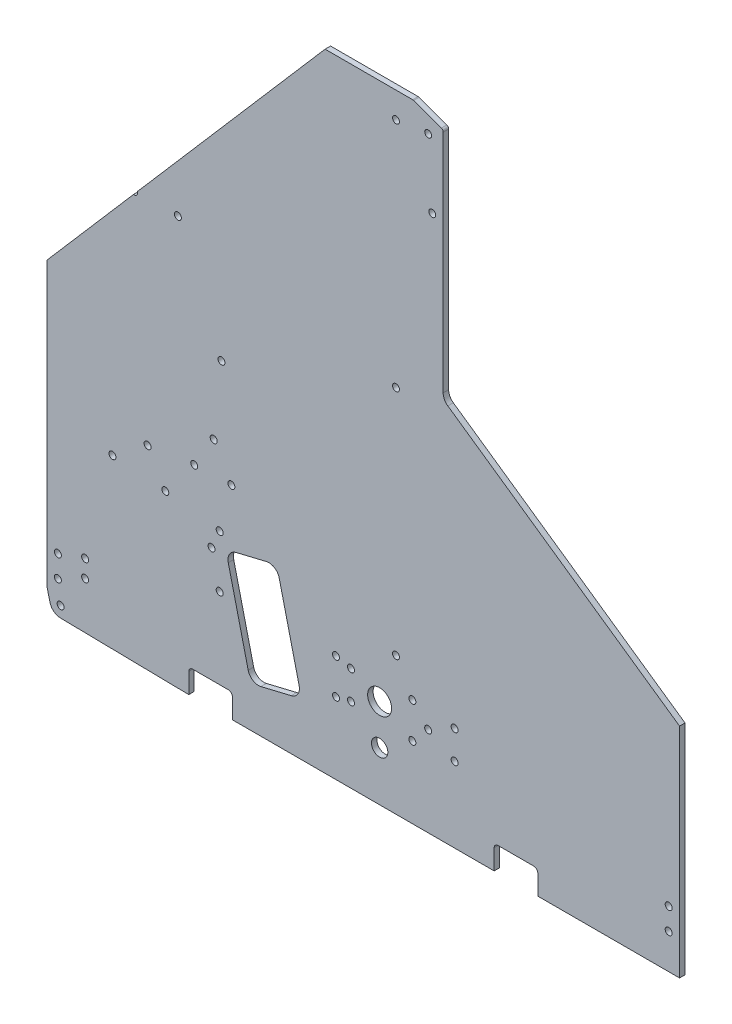
SolidWorks part; units mm, degrees
ref_plane "Front Plane" through (0, 0, 0) normal (0, 0, 1) x (1, 0, 0)
ref_plane "Top Plane" through (0, 0, 0) normal (0, 1, 0) x (1, 0, 0)
ref_plane "Right Plane" through (0, 0, 0) normal (1, 0, 0) x (0, 0, -1)
sketch "Sketch1" plane through (0, 0, 0) normal (0, 0, 1) x (1, 0, 0)
  line L0 (82.55, -20.32) -> (82.55, -6.35)
  line L2 (0, 0) -> (0, 157.48)
  line L4 (368.3, -20.32) -> (368.3, 106.68)
  line L5 (82.55, -6.35) -> (107.95, -6.35)
  line L6 (107.95, -6.35) -> (107.95, -20.32)
  line L7 (107.95, -20.32) -> (260.35, -20.32)
  line L8 (260.35, -20.32) -> (260.35, -6.35)
  line L9 (260.35, -6.35) -> (285.75, -6.35)
  line L10 (285.75, -6.35) -> (285.75, -20.32)
  line L11 (285.75, -20.32) -> (368.3, -20.32)
  line L12 (361.95, 12.7) -> (368.3, 12.7) construction
  line L13 (0, 0) -> (6.35, 0) construction
  line L14 (0.1896, -7.8901) -> (1.7771, -14.2401)
  line L15 (7.8295, -19.0491) -> (82.55, -20.32)
  line L16 (0, 0) -> (0, -6.35)
  line L17 (85.725, 97.155) -> (82.9754, 95.5675) construction
  line L18 (97.0634, 115.6163) -> (58.5686, 93.3913) construction
  line L19 (97.0634, 115.6163) -> (107.3822, 97.7437) construction
  line L20 (58.5686, 93.3913) -> (68.8873, 75.5187) construction
  line L21 (107.3822, 97.7437) -> (68.8873, 75.5187) construction
  line L22 (97.0634, 115.6163) -> (68.8873, 75.5187) construction
  line L23 (58.5686, 93.3913) -> (107.3822, 97.7437) construction
  line L24 (7.9375, -12.7) -> (95.7973, 60.4105) construction
  line L25 (203.2, 59.805) -> (203.2, 194.805) construction
  line L26 (203.2, 194.805) -> (203.2, 329.805) construction
  line L27 (355.6, 332.105) -> (330.2, 332.105) construction
  line L28 (330.2, 332.105) -> (330.2, 217.805) construction
  line L29 (330.2, 217.805) -> (355.6, 217.805) construction
  line L30 (355.6, 217.805) -> (355.6, 332.105) construction
  line L31 (203.2, 344.805) -> (203.2, 194.805) construction
  line L32 (50.8, 332.105) -> (76.2, 332.105) construction
  line L33 (76.2, 332.105) -> (76.2, 217.805) construction
  line L34 (50.8, 217.805) -> (50.8, 332.105) construction
  line L35 (76.2, 217.805) -> (50.8, 217.805) construction
  line L36 (213.2, 344.805) -> (230.6638, 338.455)
  line L37 (203.2, 344.805) -> (161.925, 344.805)
  line L38 (203.2, 344.805) -> (213.2, 344.805)
  line L39 (348.5362, 344.805) -> (413.4623, 344.805)
  line L40 (348.5362, 344.805) -> (230.6638, 344.805) construction
  line L42 (161.925, 344.805) -> (0, 157.48)
  line L44 (230.6638, 338.455) -> (230.6638, 202.565)
  line L45 (230.6638, 202.565) -> (368.3, 106.68)
  line L46 (213.2, 344.805) -> (-141.0713, 344.805) construction
  circle A0 centre (6.35, 0) radius 2.032
  circle A1 centre (6.35, 12.7) radius 2.032
  circle A2 centre (361.95, 0) radius 2.032
  circle A3 centre (361.95, 12.7) radius 2.032
  arc A5 (1.7771, -14.2401) -> (7.8295, -19.0491) centre (7.9375, -12.7) ccw
  circle A6 centre (7.9375, -12.7) radius 2.032
  arc A7 (0, -6.35) -> (0.1896, -7.8901) centre (6.35, -6.35) ccw
  circle A8 centre (38.1, 78.105) radius 2.032
  circle A9 centre (85.725, 97.155) radius 2.032
  circle A10 centre (58.5686, 93.3913) radius 2.032
  circle A11 centre (68.8873, 75.5187) radius 2.032
  circle A12 centre (107.3822, 97.7437) radius 2.032
  circle A13 centre (97.0634, 115.6163) radius 2.032
  circle A14 centre (95.7973, 60.4105) radius 2.032
  circle A15 centre (203.2, 59.805) radius 2
  circle A16 centre (203.2, 194.805) radius 2
  circle A17 centre (203.2, 329.805) radius 2
  circle A18 centre (63.5, 313.055) radius 2.032
  circle A19 centre (101.6, 157.48) radius 2.032
  circle A20 centre (355.6, 332.105) radius 2.032
  circle A21 centre (330.2, 332.105) radius 2.032
  circle A22 centre (355.6, 217.805) radius 2.032
  circle A23 centre (330.2, 217.805) radius 2.032
  circle A24 centre (50.8, 332.105) radius 2.032
  circle A25 centre (76.2, 332.105) radius 2.032
  circle A26 centre (50.8, 217.805) radius 2.032
  circle A27 centre (76.2, 217.805) radius 2.032
  circle A28 centre (221.9319, 332.105) radius 2
  circle A29 centre (224.3138, 293.243) radius 2.032
  point P82 (203.2, 344.805)
  point P83 (221.9319, 341.63)
  dimension "D6" = 4.064
  dimension "D10" = 6.35
  dimension "D11" = 4.064
  dimension "D17" = 38.1
  dimension "D27" = 4
  dimension "D31" = 4.064
  dimension "D32" = 41.275
  dimension "D36" = 4.064
  dimension "D47" = 45.212
  dimension "D48" = 4.064
  dimension "D2" = 127
  dimension "D3" = 13.97
  dimension "D4" = 25.4
  dimension "D5" = 152.4
  dimension "D7" = 12.7
  dimension "D8" = 6.35
  dimension "D9" = 20.32
  dimension "D12" = 12.7
  dimension "D13" = 1.5875
  dimension "D14" = 82.55
  dimension "D15" = 368.3
  dimension "D16" = 6.35
  dimension "D18" = 98.425
  dimension "D19" = 47.625
  dimension "D20" = 19.05
  dimension "D21" = 3.175
  dimension "D22" = 60
  dimension "D23" = 20.6375
  dimension "D24" = 44.45
  dimension "D25" = 38.1
  dimension "D26" = 114.3
  dimension "D28" = 135
  dimension "D29" = 12.7
  dimension "D30" = 15
  dimension "D33" = 63.5
  dimension "D34" = 27.4638
  dimension "D35" = 101.6
  dimension "D37" = 114.3
  dimension "D38" = 25.4
  dimension "D39" = 12.7
  dimension "D40" = 157.48
  dimension "D41" = 142.24
  dimension "D42" = 365.125
  dimension "D43" = 10
  dimension "D44" = 6.35
  dimension "D45" = 31.75
  dimension "D46" = 6.35
  dimension "D49" = 6.35
  dimension "D50" = 203.2
extrude "Boss-Extrude1" add sketch "Sketch1" along normal blind 3.175 contours L16 A7 L14 A5 L15 L2 A0 A1 A6 region at (171.4139, 119.6697, 0)
fillet "Fillet1" radius 2.286 4 edges at (285.75, -6.35, 1.5875) (107.95, -6.35, 1.5875) (260.35, -6.35, 1.5875) (82.55, -6.35, 1.5875)
fillet "Fillet2" radius 6.35 1 edges at (230.6638, 202.565, 1.5875)
sketch "Sketch2" plane through (0, 0, 0) normal (0, 0, -1) x (-1, 0, 0)
  circle A0 centre (-100.5528, 71.086) radius 2.032 construction
  circle A1 centre (-100.5528, 40.606) radius 2.032 construction
  circle A2 centre (-22.225, 18.2025) radius 2.032 construction
  circle A3 centre (-22.225, 8.0425) radius 2.032 construction
  circle A4 centre (-100.5528, 71.086) radius 2.032
  circle A5 centre (-100.5528, 40.606) radius 2.032
  circle A6 centre (-22.225, 18.2025) radius 2.032
  circle A7 centre (-22.225, 8.0425) radius 2.032
extrude "Cut-Extrude1" cut sketch "Sketch2" against normal through all
fillet "Fillet3" radius 1.5875 2 edges at (230.6638, 338.455, 1.5875) (213.2, 344.805, 1.5875)
sketch "Sketch3" plane through (0, 0, 3.175) normal (0, 0, 1) x (1, 0, 0)
  line L0 (132.9524, 63.2646) -> (132.7215, 64.2281) construction
  line L1 (128.3814, 66.8897) -> (110.6828, 62.6472) construction
  line L2 (114.5132, 58.4237) -> (126.8822, 61.3887) construction
  line L3 (108.0212, 58.3071) -> (108.2522, 57.3436) construction
  line L4 (131.2006, 57.703) -> (140.0164, 20.9265) construction
  line L5 (144.0993, 16.7636) -> (132.9524, 63.2646) construction
  line L6 (108.2522, 57.3436) -> (119.3991, 10.8426) construction
  line L7 (121.1509, 16.4042) -> (112.3351, 53.1807) construction
  line L8 (119.3991, 10.8426) -> (119.6301, 9.8791) construction
  line L9 (144.3303, 15.8001) -> (144.0993, 16.7636) construction
  line L10 (137.8383, 15.6835) -> (125.4694, 12.7185) construction
  line L11 (123.9701, 7.2175) -> (141.6687, 11.4601) construction
  line L12 (132.9524, 63.2646) -> (132.7215, 64.2281)
  line L13 (128.3814, 66.8897) -> (110.6828, 62.6472)
  line L14 (114.5132, 58.4237) -> (126.8822, 61.3887)
  line L15 (108.0212, 58.3071) -> (108.2522, 57.3436)
  line L16 (131.2006, 57.703) -> (140.0164, 20.9265)
  line L17 (144.0993, 16.7636) -> (132.9524, 63.2646)
  line L18 (108.2522, 57.3436) -> (119.3991, 10.8426)
  line L19 (121.1509, 16.4042) -> (112.3351, 53.1807)
  line L20 (119.3991, 10.8426) -> (119.6301, 9.8791)
  line L21 (144.3303, 15.8001) -> (144.0993, 16.7636)
  line L22 (137.8383, 15.6835) -> (125.4694, 12.7185)
  line L23 (123.9701, 7.2175) -> (141.6687, 11.4601)
  line L24 (127.7894, 69.3598) -> (110.0908, 65.1172)
  line L25 (105.5512, 57.715) -> (105.7822, 56.7515)
  line L26 (105.7822, 56.7515) -> (116.9291, 10.2505)
  line L27 (116.9291, 10.2505) -> (117.16, 9.287)
  line L28 (124.5622, 4.7475) -> (142.2608, 8.99)
  line L29 (146.8003, 16.3922) -> (146.5694, 17.3557)
  line L30 (146.5694, 17.3557) -> (135.4225, 63.8567)
  line L31 (135.4225, 63.8567) -> (135.1915, 64.8202)
  arc A0 (132.7215, 64.2281) -> (128.6308, 66.9403) centre (129.2206, 63.3889) ccw construction
  arc A1 (110.6828, 62.6472) -> (110.4377, 62.5791) centre (111.522, 59.1463) ccw construction
  arc A2 (128.6308, 66.9403) -> (128.3814, 66.8897) centre (129.2206, 63.3889) ccw construction
  arc A3 (110.4377, 62.5791) -> (108.0212, 58.3071) centre (111.522, 59.1463) ccw construction
  arc A4 (119.6301, 9.8791) -> (123.7207, 7.1669) centre (123.1309, 10.7183) ccw construction
  arc A5 (141.9139, 11.5281) -> (144.3303, 15.8001) centre (140.8295, 14.9609) ccw construction
  arc A6 (141.6687, 11.4601) -> (141.9139, 11.5281) centre (140.8295, 14.9609) ccw construction
  arc A7 (123.7207, 7.1669) -> (123.9701, 7.2175) centre (123.1309, 10.7183) ccw construction
  arc A8 (132.7215, 64.2281) -> (128.6308, 66.9403) centre (129.2206, 63.3889) ccw
  arc A9 (110.6828, 62.6472) -> (110.4377, 62.5791) centre (111.522, 59.1463) ccw
  arc A10 (128.6308, 66.9403) -> (128.3814, 66.8897) centre (129.2206, 63.3889) ccw
  arc A11 (110.4377, 62.5791) -> (108.0212, 58.3071) centre (111.522, 59.1463) ccw
  arc A12 (119.6301, 9.8791) -> (123.7207, 7.1669) centre (123.1309, 10.7183) ccw
  arc A13 (141.9139, 11.5281) -> (144.3303, 15.8001) centre (140.8295, 14.9609) ccw
  arc A14 (141.6687, 11.4601) -> (141.9139, 11.5281) centre (140.8295, 14.9609) ccw
  arc A15 (123.7207, 7.1669) -> (123.9701, 7.2175) centre (123.1309, 10.7183) ccw
  arc A16 (110.0908, 65.1172) -> (109.6726, 65.0012) centre (111.522, 59.1463) ccw
  arc A17 (109.6726, 65.0012) -> (105.5512, 57.715) centre (111.522, 59.1463) ccw
  arc A18 (117.16, 9.287) -> (124.1369, 4.6613) centre (123.1309, 10.7183) ccw
  arc A19 (124.1369, 4.6613) -> (124.5622, 4.7475) centre (123.1309, 10.7183) ccw
  arc A20 (142.2608, 8.99) -> (142.6789, 9.1061) centre (140.8295, 14.9609) ccw
  arc A21 (142.6789, 9.1061) -> (146.8003, 16.3922) centre (140.8295, 14.9609) ccw
  arc A22 (135.1915, 64.8202) -> (128.2147, 69.446) centre (129.2206, 63.3889) ccw
  arc A23 (128.2147, 69.446) -> (127.7894, 69.3598) centre (129.2206, 63.3889) ccw
  ellipse E0 centre (124.5974, 48.8487) end of major axis (128.5376, 61.3578) minor radius 6 (131.2006, 57.703) -> (126.8822, 61.3887) ccw construction
  ellipse E1 centre (122.2349, 48.2824) end of major axis (113.0518, 57.6456) minor radius 6 (114.5132, 58.4237) -> (112.3351, 53.1807) ccw construction
  ellipse E2 centre (127.7541, 25.2585) end of major axis (131.6942, 37.7675) minor radius 6 (121.1509, 16.4042) -> (125.4694, 12.7185) ccw construction
  ellipse E3 centre (130.1166, 25.8248) end of major axis (139.2998, 16.4616) minor radius 6 (137.8383, 15.6835) -> (140.0164, 20.9265) ccw construction
  ellipse E4 centre (124.5974, 48.8487) end of major axis (120.6573, 36.3397) minor radius 6 (131.2006, 57.703) -> (126.8822, 61.3887) ccw
  ellipse E5 centre (122.2349, 48.2824) end of major axis (131.4181, 38.9192) minor radius 6 (114.5132, 58.4237) -> (112.3351, 53.1807) ccw
  ellipse E6 centre (127.7541, 25.2585) end of major axis (131.6942, 37.7675) minor radius 6 (121.1509, 16.4042) -> (125.4694, 12.7185) ccw
  ellipse E7 centre (130.1166, 25.8248) end of major axis (139.2998, 16.4616) minor radius 6 (137.8383, 15.6835) -> (140.0164, 20.9265) ccw
  dimension "D1" = 2.54
extrude "Cut-Extrude2" cut sketch "Sketch3" against normal through all contours A22 A23 L24 A16 A17 L25 L26 L27 A18 A19 L28 A20 A21 L29 L30 L31 A15 A12 L20 L18 L15 A11 A9 L13 A10 A8 L12 L17 L21 A13 A14 L23 | A12 A15 L23 A14 A13 L21 L17 L12 A8 A10 L13 A9 A11 L15 L18 L20 E7 L22 E6 L19 E5 L14 E4 L16 | L22 E7 L16 E4 L14 E5 L19 E6 region at (137.844, 39.8506, 3.175) region at (126.1758, 37.0536, 3.175) region at (128.1544, 68.6507, 3.175)
sketch "Sketch4" plane through (0, 0, 3.175) normal (0, 0, 1) x (1, 0, 0)
  line L0 (107.3822, 97.7437) -> (68.8873, 75.5187) construction
  line L1 (168.275, 21.4312) -> (212.725, 21.4312) construction
  line L2 (168.275, 21.4312) -> (168.275, 42.0687) construction
  line L3 (168.275, 42.0687) -> (212.725, 42.0687) construction
  line L4 (212.725, 21.4312) -> (212.725, 42.0687) construction
  line L5 (168.275, 21.4312) -> (212.725, 42.0687) construction
  line L6 (168.275, 42.0687) -> (212.725, 21.4312) construction
  line L7 (97.0634, 115.6163) -> (107.3822, 97.7437) construction
  line L8 (107.95, -20.32) -> (260.35, -20.32) construction
  line L9 (193.675, 31.75) -> (177.005, 31.75) construction
  line L10 (190.5, 31.75) -> (193.675, 31.75) construction
  line L11 (6.35, 12.7) -> (361.95, 12.7) construction
  line L12 (107.95, -6.35) -> (107.95, -20.32) construction
  line L13 (193.675, 31.75) -> (220.6625, 31.75) construction
  line L14 (177.005, 23.4569) -> (177.005, 40.0431) construction
  line L15 (213.2, 44.805) -> (193.2, 44.805) construction
  line L16 (213.2, 44.805) -> (213.2, 344.805) construction
  line L17 (213.2, 344.805) -> (193.2, 344.805) construction
  line L18 (193.2, 44.805) -> (193.2, 344.805) construction
  line L19 (213.2, 44.805) -> (193.2, 344.805) construction
  line L20 (213.2, 344.805) -> (193.2, 44.805) construction
  line L21 (226.9319, 332.105) -> (226.9319, 31.75) construction
  circle A0 centre (168.275, 42.0687) radius 2.032
  circle A1 centre (212.725, 42.0687) radius 2.032
  circle A2 centre (212.725, 21.4312) radius 2.032
  circle A3 centre (168.275, 21.4312) radius 2.032
  circle A4 centre (193.675, 31.75) radius 6.985
  circle A7 centre (220.6625, 31.75) radius 14.2875 construction
  circle A8 centre (193.675, 31.75) radius 12.7 construction
  circle A9 centre (177.005, 40.0431) radius 2.032
  circle A10 centre (177.005, 23.4569) radius 2.032
  circle A11 centre (237.33, 40.0431) radius 2.032
  circle A12 centre (237.33, 23.4569) radius 2.032
  circle A13 centre (193.675, 8.4667) radius 4.7625
  circle A14 centre (221.9319, 31.75) radius 2.032
  circle A15 centre (221.9319, 31.75) radius 5 construction
  circle A16 centre (221.9319, 332.105) radius 5 construction
  point P0 (190.5, 31.75)
  point P26 (203.2, 194.805)
  point P38 (177.005, 31.75)
  point P53 (221.9319, 31.75)
  dimension "D1" = 4.064
  dimension "D4" = 13.97
  dimension "D7" = 9.525
  dimension "D10" = 25.4
  dimension "D11" = 28.575
  dimension "D16" = 10
  dimension "D17" = 4.064
  dimension "D18" = 10
  dimension "D2" = 52.07
  dimension "D3" = 3.175
  dimension "D5" = 82.55
  dimension "D6" = 26.9875
  dimension "D8" = 20
  dimension "D9" = 300
  dimension "D12" = 16.67
  dimension "D13" = 16.5862
  dimension "D14" = 60.325
  dimension "D15" = 23.2833
extrude "Cut-Extrude3" cut sketch "Sketch4" against normal through all
